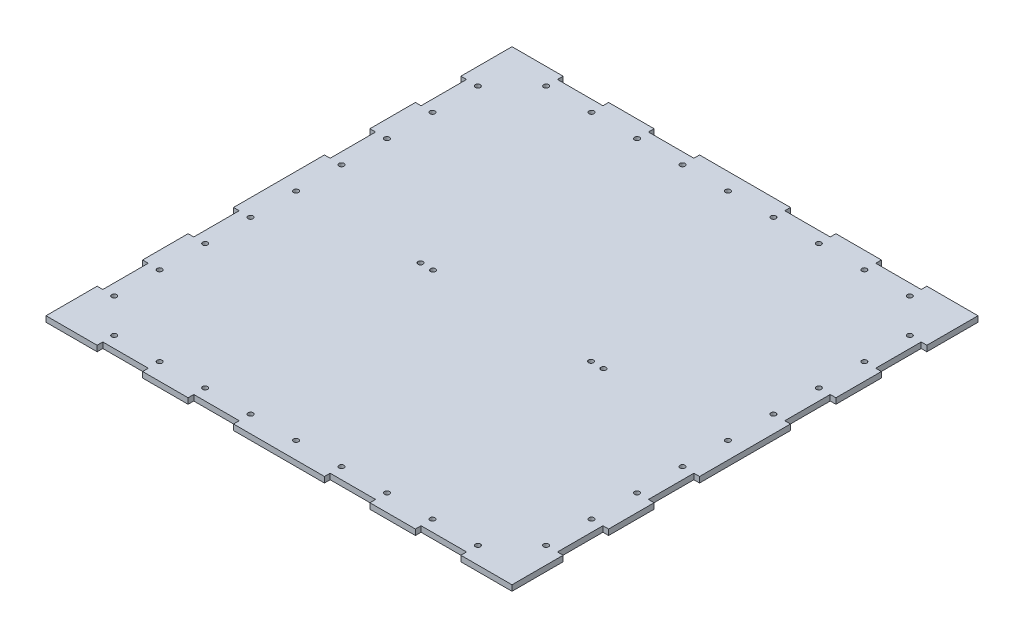
SolidWorks part; units mm, degrees
ref_plane "前视基准面" through (0, 0, 0) normal (0, 0, 1) x (1, 0, 0)
ref_plane "上视基准面" through (0, 0, 0) normal (0, 1, 0) x (1, 0, 0)
ref_plane "右视基准面" through (0, 0, 0) normal (1, 0, 0) x (0, 0, -1)
sketch "草图1" plane through (0, 0, 0) normal (0, 1, 0) x (1, 0, 0)
  line L2 (40, 200) -> (80, 200)
  line L3 (200, 40) -> (200, 80)
  line L5 (200, -40) -> (200, -80)
  line L6 (120, -200) -> (160, -200)
  line L9 (-40, -200) -> (-80, -200)
  line L10 (-200, -40) -> (-200, -80)
  line L13 (-200, 40) -> (-200, 80)
  line L14 (-40, 200) -> (-80, 200)
  line L17 (200, 205) -> (205, 205)
  line L18 (205, 200) -> (205, 205)
  line L21 (205, -200) -> (205, -205)
  line L22 (200, -205) -> (205, -205)
  line L25 (-200, -205) -> (-205, -205)
  line L26 (-205, -200) -> (-205, -205)
  line L29 (-205, 200) -> (-205, 205)
  line L30 (-200, 205) -> (-205, 205)
  line L31 (-200, 205) -> (-160, 205)
  line L32 (-160, 205) -> (-160, 200)
  line L33 (-120, 200) -> (-120, 205)
  line L34 (-120, 205) -> (-80, 205)
  line L35 (-80, 205) -> (-80, 200)
  line L36 (-80, 200) -> (-40, 200)
  line L37 (-40, 200) -> (-40, 205)
  line L38 (-40, 205) -> (40, 205)
  line L39 (40, 205) -> (40, 200)
  line L40 (80, 200) -> (80, 205)
  line L41 (80, 205) -> (120, 205)
  line L42 (120, 205) -> (120, 200)
  line L43 (120, 200) -> (160, 200)
  line L44 (160, 200) -> (160, 205)
  line L45 (160, 205) -> (200, 205)
  line L46 (205, 160) -> (200, 160)
  line L47 (200, 120) -> (205, 120)
  line L48 (205, 120) -> (205, 80)
  line L49 (205, 80) -> (200, 80)
  line L50 (200, 80) -> (200, 40)
  line L51 (200, 40) -> (205, 40)
  line L52 (205, 40) -> (205, -40)
  line L53 (205, -40) -> (200, -40)
  line L54 (200, -80) -> (205, -80)
  line L55 (205, -80) -> (205, -120)
  line L56 (205, -120) -> (200, -120)
  line L57 (200, -120) -> (200, -160)
  line L58 (200, -160) -> (205, -160)
  line L59 (205, 200) -> (205, 160)
  line L60 (205, -160) -> (205, -200)
  line L61 (160, -205) -> (160, -200)
  line L62 (120, -200) -> (120, -205)
  line L63 (120, -205) -> (80, -205)
  line L64 (80, -205) -> (80, -200)
  line L65 (80, -200) -> (40, -200)
  line L66 (40, -200) -> (40, -205)
  line L67 (40, -205) -> (-40, -205)
  line L68 (-40, -205) -> (-40, -200)
  line L69 (-80, -200) -> (-80, -205)
  line L70 (-80, -205) -> (-120, -205)
  line L71 (-120, -205) -> (-120, -200)
  line L72 (-120, -200) -> (-160, -200)
  line L73 (-160, -200) -> (-160, -205)
  line L74 (200, -205) -> (160, -205)
  line L75 (-160, -205) -> (-200, -205)
  line L76 (-205, -160) -> (-200, -160)
  line L77 (-200, -120) -> (-205, -120)
  line L78 (-205, -120) -> (-205, -80)
  line L79 (-205, -80) -> (-200, -80)
  line L80 (-200, -80) -> (-200, -40)
  line L81 (-200, -40) -> (-205, -40)
  line L82 (-205, -40) -> (-205, 40)
  line L83 (-205, 40) -> (-200, 40)
  line L84 (-200, 80) -> (-205, 80)
  line L85 (-205, 80) -> (-205, 120)
  line L86 (-205, 120) -> (-200, 120)
  line L87 (-200, 120) -> (-200, 160)
  line L88 (-200, 160) -> (-205, 160)
  line L89 (-205, -200) -> (-205, -160)
  line L90 (-205, 160) -> (-205, 200)
  line L91 (-120, 200) -> (-160, 200)
  line L92 (-200, 120) -> (-200, 160)
  line L93 (-200, -120) -> (-200, -160)
  line L94 (200, -120) -> (200, -160)
  line L95 (200, 120) -> (200, 160)
  line L96 (120, 200) -> (160, 200)
  circle A0 centre (-190, 0) radius 2.2
  circle A1 centre (-190, 40) radius 2.2
  circle A2 centre (-190, 80) radius 2.2
  circle A3 centre (-190, 120) radius 2.2
  circle A4 centre (-190, 160) radius 2.2
  circle A5 centre (-190, -160) radius 2.2
  circle A6 centre (-190, -120) radius 2.2
  circle A7 centre (-190, -80) radius 2.2
  circle A8 centre (-190, -40) radius 2.2
  circle A9 centre (0, 190) radius 2.2
  circle A10 centre (40, 190) radius 2.2
  circle A11 centre (80, 190) radius 2.2
  circle A12 centre (120, 190) radius 2.2
  circle A13 centre (160, 190) radius 2.2
  circle A14 centre (-160, 190) radius 2.2
  circle A15 centre (-120, 190) radius 2.2
  circle A16 centre (-80, 190) radius 2.2
  circle A17 centre (-40, 190) radius 2.2
  circle A18 centre (190, 0) radius 2.2
  circle A19 centre (190, -40) radius 2.2
  circle A20 centre (190, -80) radius 2.2
  circle A21 centre (190, -120) radius 2.2
  circle A22 centre (190, -160) radius 2.2
  circle A23 centre (190, 160) radius 2.2
  circle A24 centre (190, 120) radius 2.2
  circle A25 centre (190, 80) radius 2.2
  circle A26 centre (190, 40) radius 2.2
  circle A27 centre (0, -190) radius 2.2
  circle A28 centre (-40, -190) radius 2.2
  circle A29 centre (-80, -190) radius 2.2
  circle A30 centre (-120, -190) radius 2.2
  circle A31 centre (-160, -190) radius 2.2
  circle A32 centre (160, -190) radius 2.2
  circle A33 centre (120, -190) radius 2.2
  circle A34 centre (80, -190) radius 2.2
  circle A35 centre (40, -190) radius 2.2
  point P83 (0, 0)
  point P99 (0, 0)
  point P170 (0, 0)
extrude "凸台-拉伸1" add sketch "草图1" along normal blind 5 contours L47 L95 L46 L59 L18 L17 L45 L44 L43 L42 L41 L40 L2 L39 L38 L37 L14 L35 L34 L33 L91 L32 L31 L30 L29 L90 L88 L87 L86 L85 L84 L13 L83 L82 L81 L10 L79 L78 L77 L93 L76 L89 L26 L25 L75 L73 L72 L71 L70 L69 L9 region at (0, 0, 0)
sketch "草图2" plane through (0, 5, 0) normal (0, 1, 0) x (1, 0, 0)
  circle A0 centre (69.5, 0) radius 2.2
  circle A1 centre (-80.5, 0) radius 2.2
  circle A2 centre (80.5, 0) radius 2.2
  circle A3 centre (-69.5, 0) radius 2.2
  point P13 (0, 0)
  dimension "D1" = 2
extrude "切除-拉伸2" cut sketch "草图2" against normal blind 20
